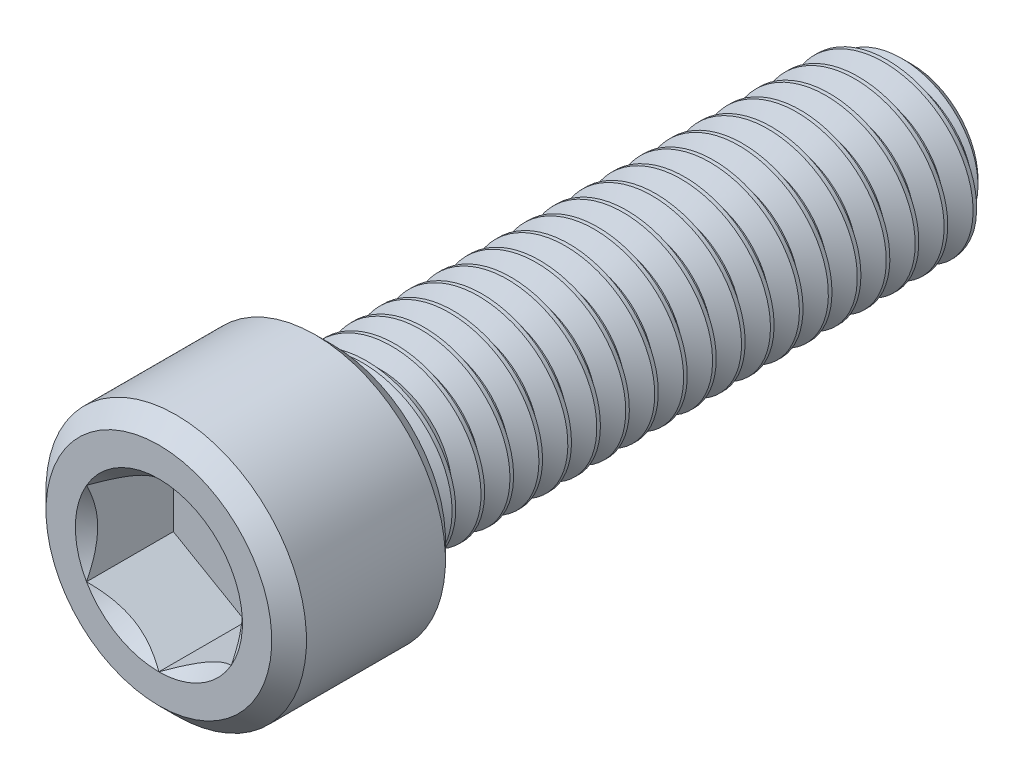
SolidWorks part; units mm, degrees
ref_plane "Front Plane" through (0, 0, 0) normal (0, 0, 1) x (1, 0, 0)
ref_plane "Top Plane" through (0, 0, 0) normal (0, 1, 0) x (1, 0, 0)
ref_plane "Right Plane" through (0, 0, 0) normal (1, 0, 0) x (0, 0, -1)
sketch "Sketch1" plane through (0, 0, 0) normal (1, 0, 0) x (0, 0, -1)
  line L0 (20.6375, 0) -> (-20.6375, 0) construction
  line L1 (-20.6375, 0) -> (-20.6375, 6.1912)
  line L2 (-20.6375, 6.1912) -> (-19.685, 7.1437)
  line L3 (-19.685, 7.1437) -> (-12.065, 7.1437)
  line L4 (-12.065, 7.1437) -> (-11.1125, 6.1912)
  line L5 (-11.1125, 6.1912) -> (-11.1125, 4.7625)
  line L6 (-11.1125, 4.7625) -> (19.5263, 4.7625)
  line L7 (19.5263, 4.7625) -> (20.6375, 3.6513)
  line L8 (20.6375, 3.6513) -> (20.6375, 0)
  line L9 (20.5383, 4.9344) -> (22.1258, 4.9344) construction
  line L10 (22.1258, 4.9344) -> (21.332, 3.5595) construction
  line L11 (21.332, 3.5595) -> (20.5383, 4.9344) construction
  line L12 (20.6375, 4.7625) -> (22.0266, 4.7625) construction
  line L13 (21.332, 4.9344) -> (21.332, 4.7625) construction
  line L14 (21.2328, 3.7314) -> (21.4312, 3.7314) construction
  line L15 (21.332, 3.7314) -> (21.332, 3.5595) construction
  line L16 (20.5879, 4.8484) -> (22.0762, 4.8484)
  line L17 (22.0762, 4.8484) -> (21.4312, 3.7314)
  line L18 (21.4312, 3.7314) -> (21.2328, 3.7314)
  line L19 (21.2328, 3.7314) -> (20.5879, 4.8484)
  line L20 (19.5263, -4.7625) -> (16.6688, -4.7625) construction
  point P4 (0, 0)
  point P25 (21.332, 4.8484)
  point P26 (20.6375, 4.7625)
  point P33 (16.6688, -4.7625)
  dimension "Head Ht" = 9.525
  dimension "Screw Size" = 9.525
  dimension "Head Dia" = 14.2875
  dimension "D1" = 45
  dimension "D2" = 45
  dimension "D3" = 0.9525
  dimension "D4" = 0.9525
  dimension "Pitch" = 1.5875
  dimension "D5" = 0.1984
  dimension "D6" = 1.1113
  dimension "D7" = 2.8575
  dimension "Length" = 31.75
sketch "Sketch2" plane through (0, 0, 0) normal (0, 0, 1) x (1, 0, 0)
  line L1 (0, 4.5827) -> (-3.9688, 2.2914)
  line L2 (-3.9688, 2.2914) -> (-3.9687, -2.2914)
  line L3 (-3.9687, -2.2914) -> (0, -4.5827)
  line L4 (0, -4.5827) -> (3.9688, -2.2914)
  line L5 (3.9688, -2.2914) -> (3.9688, 2.2914)
  line L6 (3.9688, 2.2914) -> (0, 4.5827)
  circle A0 centre (0, 0) radius 3.9688 construction
  circle A1 centre (0, 0) radius 7.1437
  point P1 (0, 7.1437)
  dimension "D1" = 14.2875
  dimension "Drive Size" = 7.9375
sketch "Sketch3" plane through (0, 0, 0) normal (1, 0, 0) x (0, 0, -1)
  line L0 (20.6375, 0) -> (-20.6375, 0) construction
  line L1 (-20.6375, 0) -> (-20.6375, 6.1912) construction
  line L2 (-20.6375, 6.1912) -> (-19.685, 7.1437) construction
  line L3 (-19.685, 7.1437) -> (-12.065, 7.1437) construction
  line L4 (-12.065, 7.1437) -> (-11.1125, 6.1912) construction
  line L5 (-11.1125, 6.1912) -> (-11.1125, 4.7625) construction
  line L6 (-11.1125, 4.7625) -> (19.5263, 4.7625) construction
  line L7 (19.5263, 4.7625) -> (20.6375, 3.6513) construction
  line L8 (20.6375, 3.6513) -> (20.6375, 0) construction
  line L9 (20.6375, 0) -> (-20.6375, 0)
  line L10 (-20.6375, 0) -> (-20.6375, 6.1912)
  line L11 (-20.6375, 6.1912) -> (-19.685, 7.1437)
  line L12 (-19.685, 7.1437) -> (-12.065, 7.1437)
  line L13 (-12.065, 7.1437) -> (-11.1125, 6.1912)
  line L14 (-11.1125, 6.1912) -> (-11.1125, 4.7625)
  line L15 (-11.1125, 4.7625) -> (19.5263, 4.7625)
  line L16 (19.5263, 4.7625) -> (20.6375, 3.6513)
  line L17 (20.6375, 3.6513) -> (20.6375, 0)
revolve "Revolve1" add sketch "Sketch3" angle 360 about L0
sketch "Sketch4" plane through (0, 0, 20.6375) normal (0, 0, 1) x (1, 0, 0)
  line L0 (0, -4.5827) -> (3.9688, -2.2914) construction
  line L1 (3.9688, -2.2914) -> (3.9688, 2.2914) construction
  line L2 (3.9688, 2.2914) -> (0, 4.5827) construction
  line L3 (0, 4.5827) -> (-3.9688, 2.2914) construction
  line L4 (-3.9688, 2.2914) -> (-3.9687, -2.2914) construction
  line L5 (-3.9687, -2.2914) -> (0, -4.5827) construction
  line L6 (0, -4.5827) -> (3.9688, -2.2914)
  line L7 (3.9688, -2.2914) -> (3.9688, 2.2914)
  line L8 (3.9688, 2.2914) -> (0, 4.5827)
  line L9 (0, 4.5827) -> (-3.9688, 2.2914)
  line L10 (-3.9688, 2.2914) -> (-3.9687, -2.2914)
  line L11 (-3.9687, -2.2914) -> (0, -4.5827)
extrude "Cut-Extrude1" cut sketch "Sketch4" against normal blind 4.7625
sketch "Sketch5" plane through (0, 0, 20.6375) normal (0, 0, 1) x (1, 0, 0)
  circle A0 centre (0, 0) radius 4.5827
extrude "Cut-Extrude3" cut sketch "Sketch5" against normal through all draft 45
split "Split1" bodies to split 107 resulting bodies 108 109 split by face at (0, 6.1912, 11.1125)
sketch "Sketch6" plane through (0, 0, -20.6375) normal (0, 0, -1) x (-1, 0, 0)
  circle A0 centre (0, 0) radius 4.7625 construction
  circle A1 centre (0, 0) radius 4.7625
curve "Helix/Spiral1" pitch 1.5875 height 33.3375 radius 4.7625 centre (0, 0, -20.6375) axis (0, 0, 1) start towards (0, 1, 0)
sketch "Sketch7" plane through (0, 0, 0) normal (1, 0, 0) x (0, 0, -1)
  line L0 (20.5879, 4.8484) -> (22.0762, 4.8484) construction
  line L1 (22.0762, 4.8484) -> (21.4312, 3.7314) construction
  line L2 (21.4312, 3.7314) -> (21.2328, 3.7314) construction
  line L3 (21.2328, 3.7314) -> (20.5879, 4.8484) construction
  line L4 (20.5879, 4.8484) -> (22.0762, 4.8484)
  line L5 (22.0762, 4.8484) -> (21.4312, 3.7314)
  line L6 (21.4312, 3.7314) -> (21.2328, 3.7314)
  line L7 (21.2328, 3.7314) -> (20.5879, 4.8484)
sweep "Cut-Sweep1" cut profiles "Sketch7" path "Helix/Spiral1" align with end faces yes
sketch "Sketch8" plane through (0, 0, 11.1125) normal (0, 0, -1) x (-1, 0, 0)
  circle A1 centre (0, 0) radius 4.7625
extrude "Boss-Extrude1" add sketch "Sketch8" along normal up to next (31.75 mm away) draft 20
equation "\"D3@Sketch1\"=\"Head Ht@Sketch1\"/10"
equation "\"D4@Sketch1\"=\"Head Ht@Sketch1\"/10"
equation "\"D5@Sketch1\"=\"Pitch@Sketch1\"/8"
equation "\"D6@Sketch1\"=\"Pitch@Sketch1\"*.7"
equation "\"D7@Sketch1\"=\"Pitch@Sketch1\"*2.5-\"D6@Sketch1\""
equation "\"D1@Cut-Extrude1\"=\"Head Ht@Sketch1\"/2"
equation "\"D4@Helix/Spiral1\"=\"Pitch@Sketch1\""
equation "\"D3@Helix/Spiral1\"=\"Length@Sketch1\"+\"D4@Helix/Spiral1\""
